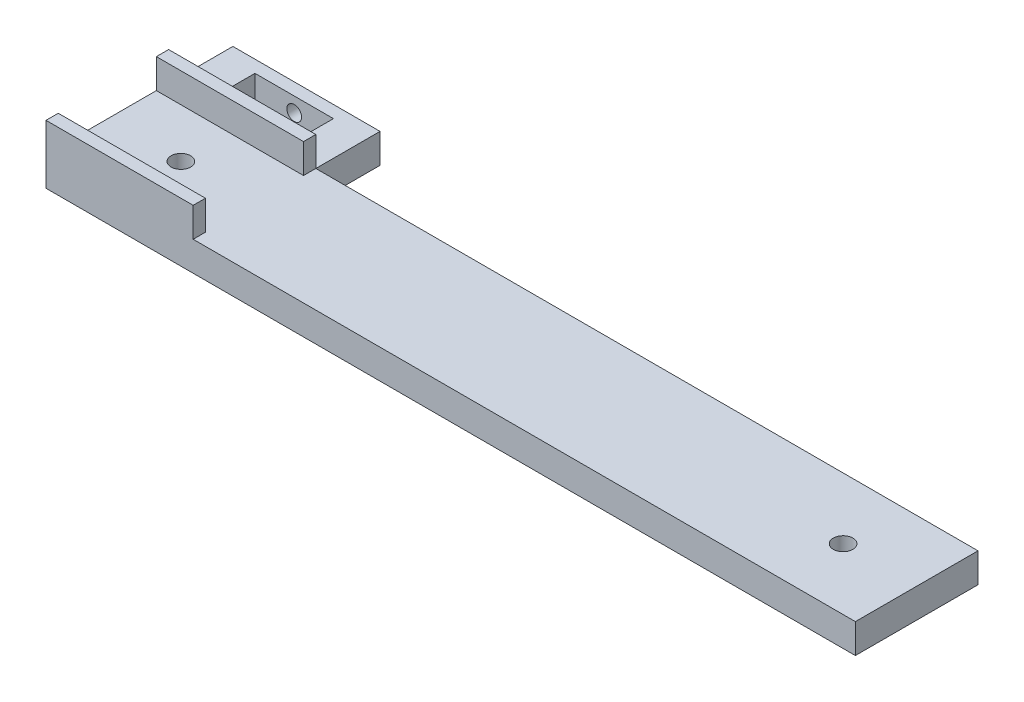
SolidWorks part; units mm, degrees
ref_plane "Front" through (0, 0, 0) normal (0, 0, 1) x (1, 0, 0)
ref_plane "Top" through (0, 0, 0) normal (0, 1, 0) x (1, 0, 0)
ref_plane "Right" through (0, 0, 0) normal (1, 0, 0) x (0, 0, -1)
sketch "Sketch1" plane through (0, 0, 0) normal (0, 1, 0) x (1, 0, 0)
  line L0 (0, -20) -> (0, -22.5)
  line L1 (0, 0) -> (-30, 0)
  line L2 (0, 0) -> (0, -20)
  line L3 (0, -20) -> (-30, -20)
  line L4 (-30, 0) -> (-30, -20)
  line L5 (0, -22.5) -> (-30, -22.5)
  line L6 (-30, -22.5) -> (-30, -20)
  line L7 (0, 0) -> (-7, 0)
  line L8 (-30, 0) -> (0, 0)
  line L9 (-30, 0) -> (-30, 2.5)
  line L10 (-30, 2.5) -> (0, 2.5)
  line L11 (0, 0) -> (0, 2.5)
  line L12 (-30, 0) -> (-23, 0)
  line L13 (-30, 2.5) -> (-30, 13.1)
  line L14 (-30, 13.1) -> (0, 13.1)
  line L15 (0, 13.1) -> (0, 2.5)
  line L16 (0, 13.1) -> (0, 15.6)
  line L17 (0, 15.6) -> (-30, 15.6)
  line L18 (-30, 15.6) -> (-30, 13.1)
  line L19 (-7, 0) -> (-7, 15.6)
  line L20 (-23, 0) -> (-23, 15.6)
  line L21 (-15, -20) -> (-15, 0)
  line L22 (-15, 0) -> (-15, -10)
  line L23 (-15, -10) -> (-165, -10)
  line L24 (-165, -10) -> (-165, -22.5)
  line L25 (-165, -22.5) -> (-165, 2.5)
  line L26 (-165, 2.5) -> (-30, 2.5)
  line L27 (-165, -22.5) -> (-30, -22.5)
  line L28 (-165, -10) -> (-150, -10)
  line L29 (135, -22.5) -> (135, 2.5)
  line L30 (135, 2.5) -> (0, 2.5)
  line L31 (135, -22.5) -> (0, -22.5)
  circle A0 centre (-150, -10) radius 2
  circle A1 centre (120, -10) radius 2
  dimension "D10" = 15
  dimension "D1" = 20
  dimension "D2" = 2.5
  dimension "D3" = 2.5
  dimension "D4" = 30
  dimension "D5" = 7
  dimension "D6" = 7
  dimension "D7" = 10.6
  dimension "D8" = 2.5
  dimension "D9" = 150
extrude "Boss-Extrude1" add sketch "Sketch1" along normal blind 6 contours L1 L8 L4 L3 L2 | L6 L5 L0 L3 | L20 L1 L19 L10 | L19 L1 L11 L10 | L19 L10 L15 L14 | L19 L14 L16 L17 | L20 L14 L19 L17 | L14 L20 L17 L18 | L10 L20 L14 L13 | L8 L20 L10 L9 | L21 L23 L4 L3 | L23 L21 L8 L4 | L31 L29 L30 L11 L2 L0 A1 region at (67.3038, 0, 10) region at (-7.5, 0, 10) region at (-15, 0, 21.25) region at (-3.5, 0, -1.25) region at (-22.5, 0, 15) region at (-15, 0, -1.25) region at (-3.5, 0, -7.8) region at (-22.5, 0, 5) region at (-3.5, 0, -14.35) region at (-26.5, 0, -1.25) region at (-26.5, 0, -7.8) region at (-15, 0, -14.35) region at (-26.5, 0, -14.35)
extrude "Boss-Extrude2" add sketch "Sketch1<3>" along normal blind 12 contours L19 L1 L11 L10 | L20 L1 L19 L10 | L6 L5 L0 L3 | L8 L20 L10 L9 region at (-15, 0, 21.25) region at (-3.5, 0, -1.25) region at (-15, 0, -1.25) region at (-26.5, 0, -1.25)
sketch "Sketch1<3>" plane through (0, 0, 0) normal (0, 1, 0) x (1, 0, 0) same geometry as "Sketch1"
sketch "Sketch3" plane through (0, 0, -15.6) normal (0, 0, -1) x (-1, 0, 0)
  line L0 (30, 3) -> (23, 3)
  line L1 (30, 6) -> (30, 0) construction
  line L2 (23, 3) -> (15, 3)
  circle A0 centre (15, 3) radius 1.5
  dimension "D1" = 7
  dimension "D2" = 8
extrude "Cut-Extrude2" cut sketch "Sketch3" against normal blind 5 contours A0
sketch "Sketch4" plane through (0, 0, -2.5) normal (0, 0, -1) x (-1, 0, 0)
  line L0 (23, 3) -> (15, 3)
  line L1 (23, 6) -> (23, 0) construction
  line L3 (17.8868, 3) -> (16.4434, 5.5)
  line L4 (16.4434, 5.5) -> (13.5566, 5.5)
  line L5 (13.5566, 5.5) -> (12.1132, 3)
  line L6 (12.1132, 3) -> (13.5566, 0.5)
  line L7 (13.5566, 0.5) -> (16.4434, 0.5)
  line L8 (16.4434, 0.5) -> (17.8868, 3)
  circle A0 centre (15, 3) radius 2.5 construction
  dimension "D1" = 8
extrude "Cut-Extrude3" cut sketch "Sketch4" against normal blind 2.5 contours L7 L8 L3 L4 L5 L6 region at (-17.0989, 1.7882, -2.5)
sketch "Sketch2" plane through (0, 6, 0) normal (0, 1, 0) x (1, 0, 0)
  line L0 (-30, -10) -> (0, -10)
  line L1 (-30, 15.6) -> (-30, 2.5) construction
  line L2 (0, 0) -> (0, -20) construction
  circle A0 centre (-15, -10) radius 2
extrude "Cut-Extrude1" cut sketch "Sketch2" against normal through all contours L0 A0 | L0 A0 region at (-15, 6, 9.1512) region at (-15, 6, 10.8488)
